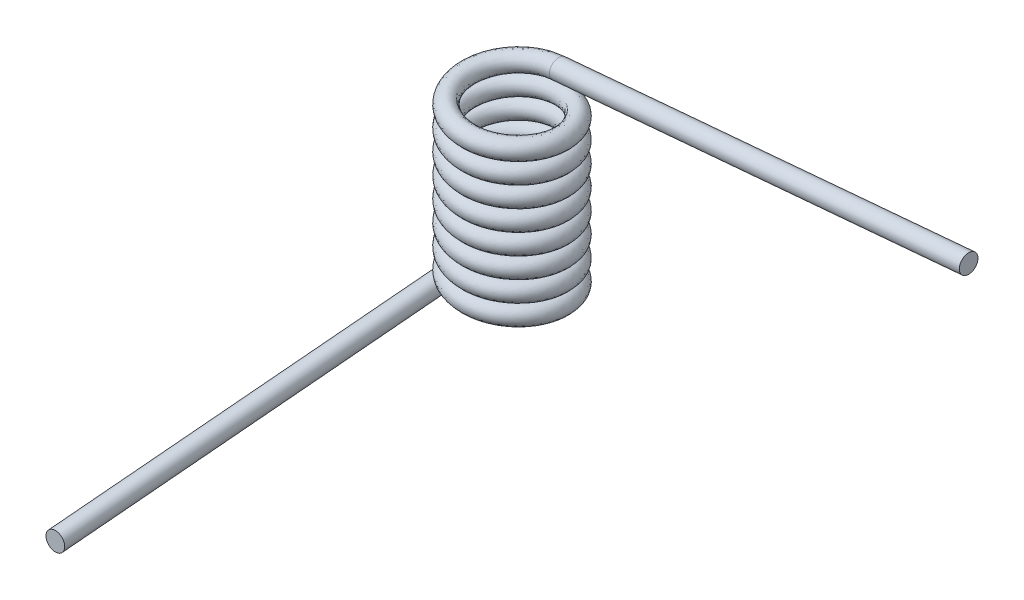
SolidWorks part; units mm, degrees
ref_plane "Front Plane" through (0, 0, 0) normal (0, 0, 1) x (1, 0, 0)
ref_plane "Top Plane" through (0, 0, 0) normal (0, 1, 0) x (1, 0, 0)
ref_plane "Right Plane" through (0, 0, 0) normal (1, 0, 0) x (0, 0, -1)
sketch "Sketch1" plane through (0, 0, 0) normal (0, 1, 0) x (1, 0, 0)
  circle A0 centre (0, 0) radius 5
  dimension "D1" = 10
curve "Helix/Spiral1" pitch 2.1875 height 17.5 turns 8
sketch "Sketch2" plane through (0, 0, 0) normal (1, 0, 0) x (0, 0, -1)
  circle A0 centre (5, 0) radius 1
  spline S0 degree 3 poles (5, 0) (5, 0.0453) (4.7397, 0.1369) (3.6276, 0.2734) (1.9632, 0.4102) (0, 0.5469) (-1.9632, 0.6836) (-3.6276, 0.8203) (-4.7397, 0.957) (-5.1302, 1.0937) (-4.7397, 1.2305) (-3.6276, 1.3672) (-1.9632, 1.5039) (0, 1.6406) (1.9632, 1.7773) (3.6276, 1.9141) (4.7397, 2.0508) (5.1302, 2.1875) (4.7397, 2.3242) (3.6276, 2.4609) (1.9632, 2.5977) (0, 2.7344) (-1.9632, 2.8711) (-3.6276, 3.0078) (-4.7397, 3.1445) (-5.1302, 3.2813) (-4.7397, 3.418) (-3.6276, 3.5547) (-1.9632, 3.6914) (0, 3.8281) (1.9632, 3.9648) (3.6276, 4.1016) (4.7397, 4.2383) (5.1302, 4.375) (4.7397, 4.5117) (3.6276, 4.6484) (1.9632, 4.7852) (0, 4.9219) (-1.9632, 5.0586) (-3.6276, 5.1953) (-4.7397, 5.332) (-5.1302, 5.4688) (-4.7397, 5.6055) (-3.6276, 5.7422) (-1.9632, 5.8789) (0, 6.0156) (1.9632, 6.1523) (3.6276, 6.2891) (4.7397, 6.4258) (5.1302, 6.5625) (4.7397, 6.6992) (3.6276, 6.8359) (1.9632, 6.9727) (0, 7.1094) (-1.9632, 7.2461) (-3.6276, 7.3828) (-4.7397, 7.5195) (-5.1302, 7.6562) (-4.7397, 7.793) (-3.6276, 7.9297) (-1.9632, 8.0664) (0, 8.2031) (1.9632, 8.3398) (3.6276, 8.4766) (4.7397, 8.6133) (5.1302, 8.75) (4.7397, 8.8867) (3.6276, 9.0234) (1.9632, 9.1602) (0, 9.2969) (-1.9632, 9.4336) (-3.6276, 9.5703) (-4.7397, 9.707) (-5.1302, 9.8438) (-4.7397, 9.9805) (-3.6276, 10.1172) (-1.9632, 10.2539) (0, 10.3906) (1.9632, 10.5273) (3.6276, 10.6641) (4.7397, 10.8008) (5.1302, 10.9375) (4.7397, 11.0742) (3.6276, 11.2109) (1.9632, 11.3477) (0, 11.4844) (-1.9632, 11.6211) (-3.6276, 11.7578) (-4.7397, 11.8945) (-5.1302, 12.0313) (-4.7397, 12.168) (-3.6276, 12.3047) (-1.9632, 12.4414) (0, 12.5781) (1.9632, 12.7148) (3.6276, 12.8516) (4.7397, 12.9883) (5.1302, 13.125) (4.7397, 13.2617) (3.6276, 13.3984) (1.9632, 13.5352) (0, 13.6719) (-1.9632, 13.8086) (-3.6276, 13.9453) (-4.7397, 14.082) (-5.1302, 14.2188) (-4.7397, 14.3555) (-3.6276, 14.4922) (-1.9632, 14.6289) (0, 14.7656) (1.9632, 14.9023) (3.6276, 15.0391) (4.7397, 15.1758) (5.1302, 15.3125) (4.7397, 15.4492) (3.6276, 15.5859) (1.9632, 15.7227) (0, 15.8594) (-1.9632, 15.9961) (-3.6276, 16.1328) (-4.7397, 16.2695) (-5.1302, 16.4063) (-4.7397, 16.543) (-3.6276, 16.6797) (-1.9632, 16.8164) (0, 16.9531) (1.9632, 17.0898) (3.6276, 17.2266) (4.7397, 17.3631) (5, 17.4547) (5, 17.5) knots 0 0 0 0 0.007812 0.015625 0.023437 0.03125 0.039062 0.046875 0.054687 0.0625 0.070312 0.078125 0.085937 0.09375 0.101562 0.109375 0.117187 0.125 0.132812 0.140625 0.148437 0.15625 0.164062 0.171875 0.179687 0.1875 0.195312 0.203125 0.210937 0.21875 0.226562 0.234375 0.242187 0.25 0.257812 0.265625 0.273437 0.28125 0.289062 0.296875 0.304687 0.3125 0.320312 0.328125 0.335937 0.34375 0.351562 0.359375 0.367187 0.375 0.382812 0.390625 0.398437 0.40625 0.414062 0.421875 0.429687 0.4375 0.445312 0.453125 0.460937 0.46875 0.476562 0.484375 0.492187 0.5 0.507812 0.515625 0.523437 0.53125 0.539062 0.546875 0.554687 0.5625 0.570312 0.578125 0.585937 0.59375 0.601562 0.609375 0.617187 0.625 0.632812 0.640625 0.648437 0.65625 0.664062 0.671875 0.679687 0.6875 0.695312 0.703125 0.710937 0.71875 0.726562 0.734375 0.742187 0.75 0.757812 0.765625 0.773437 0.78125 0.789062 0.796875 0.804687 0.8125 0.820312 0.828125 0.835937 0.84375 0.851562 0.859375 0.867187 0.875 0.882812 0.890625 0.898438 0.90625 0.914062 0.921875 0.929688 0.9375 0.945312 0.953125 0.960938 0.96875 0.976562 0.984375 0.992188 1 1 1 1 construction
  dimension "D1" = 2
  dimension "D2" = 5
sweep "Sweep1" add profiles "Sketch2" path "Helix/Spiral1"
sketch "Sketch11" plane through (0, 0, 0) normal (0, 0, 1) x (1, 0, 0)
  line L0 (0, 17.5) -> (5.4233, 17.9745)
  line L1 (0, 16.5) -> (0, 18.5) construction
  dimension "D1" = 85
sketch "Sketch3" plane through (0, 0, 0) normal (1, 0, 0) x (0, 0, -1)
  circle A0 centre (5, 17.5) radius 1
extrude "Boss-Extrude1" add sketch "Sketch3" along direction (0.9962, 0.0872, 0) on the side of the normal blind 44
sketch "Sketch5" plane through (0, 0, 0) normal (-1, 0, 0) x (0, 0, 1)
  circle A0 centre (-5, 0) radius 1
  dimension "D1" = 2
  dimension "D2" = 5
sketch "Sketch8" plane through (0, 0, 0) normal (0, 1, 0) x (1, 0, 0)
  circle A0 centre (0, 0) radius 5
  dimension "D1" = 10
curve "Helix/Spiral2" pitch 2.1875 height 0.5469 turns 0.25
sweep "Sweep3" add profiles "Sketch5" path "Helix/Spiral2"
sketch "Sketch10" plane through (0, 0, 0) normal (1, 0, 0) x (0, 0, -1)
  line L0 (0, -0.5469) -> (-4.6131, -0.9505)
  line L1 (0, 0.4531) -> (0, -1.5469) construction
  dimension "D1" = 85
sketch "Sketch9" plane through (0, 0, 0) normal (0, 0, 1) x (1, 0, 0)
  circle A0 centre (-5, -0.5469) radius 1
extrude "Boss-Extrude3" add sketch "Sketch9" along direction (0, -0.0872, 0.9962) on the side of the normal blind 44
